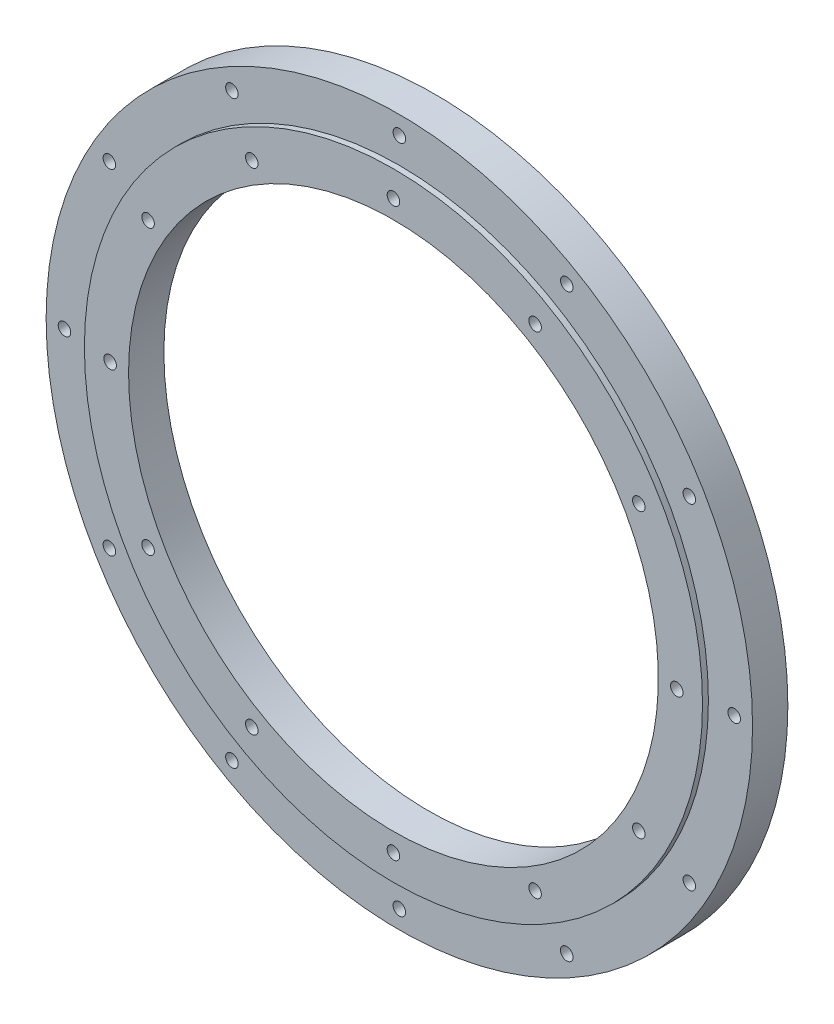
SolidWorks part; units mm, degrees
ref_plane "Front Plane" through (0, 0, 0) normal (0, 0, 1) x (1, 0, 0)
ref_plane "Top Plane" through (0, 0, 0) normal (0, 1, 0) x (1, 0, 0)
ref_plane "Right Plane" through (0, 0, 0) normal (1, 0, 0) x (0, 0, -1)
sketch "Sketch2" plane through (0, 0, 0) normal (0, 0, 1) x (1, 0, 0)
  circle A0 centre (0, 0) radius 76.2
  circle A1 centre (0, 0) radius 57.15
  circle A2 centre (0, 0) radius 66.675
  dimension "D1" = 114.3
  dimension "D2" = 133.35
  dimension "D3" = 152.4
extrude "Boss-Extrude1" add sketch "Sketch2" along normal blind 7.62 contours A0 A2 region at (-74.0447, 0, 0)
extrude "Boss-Extrude2" add sketch "Sketch2<3>" along normal blind 7.62 from offset 1.27 contours A2 A1 region at (-64.7891, 0, 0)
sketch "Sketch2<3>" plane through (0, 0, 0) normal (0, 0, 1) x (1, 0, 0) same geometry as "Sketch2"
hole_wizard "#6-32 Tapped Hole1" positions "3DSketch1" profile "Sketch3" tap size "#6-32" standard "ANSI Inch" end condition through all
sketch3d "3DSketch1"
  line L0 (0, 0, 8.89) -> (0, 0, 7.62) construction
  line L1 (0, 0, 8.89) -> (0, 0, 1.27) construction
  line L2 (0, 0, 8.89) -> (0, 66.675, 8.89) construction
  line L3 (0, 0, 8.89) -> (-33.3375, 57.7422, 8.89) construction
  line L4 (0, 0, 8.89) -> (-57.7422, 33.3375, 8.89) construction
  line L5 (0, 0, 8.89) -> (-66.675, 0, 8.89) construction
  line L6 (0, 0, 8.89) -> (-57.7422, -33.3375, 8.89) construction
  line L7 (0, 0, 8.89) -> (-33.3375, -57.7422, 8.89) construction
  line L8 (0, 0, 8.89) -> (0, -66.675, 8.89) construction
  line L9 (0, 0, 8.89) -> (33.3375, -57.7422, 8.89) construction
  line L10 (0, 0, 8.89) -> (57.7422, -33.3375, 8.89) construction
  line L11 (0, 0, 8.89) -> (66.675, 0, 8.89) construction
  line L12 (0, 0, 8.89) -> (57.7422, 33.3375, 8.89) construction
  line L13 (0, 0, 8.89) -> (33.3375, 57.7422, 8.89) construction
  circle A0 centre (0, 0, 8.89) radius 61.1251
  circle A1 centre (0, 0, 8.89) radius 66.675 construction
  point P0 (-30.5625, 52.9359, 8.89)
  point P2 (-52.9359, 30.5626, 8.89)
  point P4 (-61.1251, 0, 8.89)
  point P6 (-52.9359, -30.5625, 8.89)
  point P8 (-30.5626, -52.9359, 8.89)
  point P10 (0, -61.1251, 8.89)
  point P12 (30.5625, -52.9359, 8.89)
  point P14 (52.9359, -30.5626, 8.89)
  point P16 (61.1251, 0, 8.89)
  point P18 (52.9359, 30.5625, 8.89)
  point P20 (30.5626, 52.9359, 8.89)
  point P22 (0, 61.1251, 8.89)
  point P27 (0, 0, 70.0151)
  point P37 (0, 0, 75.565)
  dimension "D1" = 122.2502
  dimension "D2" = 30
  dimension "D3" = 30
  dimension "D4" = 30
  dimension "D5" = 30
  dimension "D6" = 30
  dimension "D7" = 30
  dimension "D8" = 30
  dimension "D9" = 30
  dimension "D10" = 30
  dimension "D11" = 30
  dimension "D12" = 30
  dimension "D13" = 30
sketch "Sketch3" plane through (-30.5625, 52.9359, 8.89) normal (1, 0, 0) x (0, -1, 0)
  line L0 (0, 0) -> (0, 8.89)
  line L1 (0, 8.89) -> (1.3525, 8.89)
  line L2 (1.3525, 8.89) -> (1.3525, 0)
  line L5 (1.3525, 0) -> (0, 0)
  line L11 (0, -6.35) -> (0, 107.95) construction
  dimension "Thru Tap Drill Dia." = 2.7051
  dimension "Thru Tap Drill Depth" = 8.89
cosmetic thread "Hole Thread1" parameters "D2"=3.5052
cosmetic thread "Hole Thread2" parameters "D2"=3.5052
cosmetic thread "Hole Thread3" parameters "D2"=3.5052
cosmetic thread "Hole Thread4" parameters "D2"=3.5052
cosmetic thread "Hole Thread5" parameters "D2"=3.5052
cosmetic thread "Hole Thread6" parameters "D2"=3.5052
cosmetic thread "Hole Thread7" parameters "D2"=3.5052
cosmetic thread "Hole Thread8" parameters "D2"=3.5052
cosmetic thread "Hole Thread9" parameters "D2"=3.5052
cosmetic thread "Hole Thread10" parameters "D2"=3.5052
cosmetic thread "Hole Thread11" parameters "D2"=3.5052
cosmetic thread "Hole Thread12" parameters "D2"=3.5052
hole_wizard "#6-32 Tapped Hole2" positions "3DSketch2" profile "Sketch4" tap size "#6-32" standard "ANSI Inch" end condition through all
sketch3d "3DSketch2"
  line L0 (0, 0, 7.62) -> (0, 0, 0) construction
  line L1 (0, 0, 8.89) -> (0, 0, 7.62) construction
  line L20 (0, 0, 7.62) -> (0, 76.2, 7.62) construction
  line L21 (0, 0, 7.62) -> (-38.1, 65.9911, 7.62) construction
  line L22 (0, 0, 7.62) -> (-65.9911, 38.1, 7.62) construction
  line L23 (0, 0, 7.62) -> (-76.2, 0, 7.62) construction
  line L24 (0, 0, 7.62) -> (-65.9911, -38.1, 7.62) construction
  line L25 (0, 0, 7.62) -> (-38.1, -65.9911, 7.62) construction
  line L26 (0, 0, 7.62) -> (0, -76.2, 7.62) construction
  line L27 (0, 0, 7.62) -> (38.1, -65.9911, 7.62) construction
  line L28 (0, 0, 7.62) -> (65.9911, -38.1, 7.62) construction
  line L29 (0, 0, 7.62) -> (76.2, 0, 7.62) construction
  line L30 (0, 0, 7.62) -> (65.9911, 38.1, 7.62) construction
  line L31 (0, 0, 7.62) -> (38.1, 65.9911, 7.62) construction
  circle A1 centre (0, 0, 7.62) radius 72.2376
  circle A3 centre (0, 0, 7.62) radius 76.2 construction
  point P0 (0, 72.2376, 7.62)
  point P2 (-36.1188, 62.5596, 7.62)
  point P4 (-62.5596, 36.1188, 7.62)
  point P6 (-72.2376, 0, 7.62)
  point P8 (-62.5596, -36.1188, 7.62)
  point P10 (-36.1188, -62.5596, 7.62)
  point P12 (0, -72.2376, 7.62)
  point P14 (36.1188, -62.5596, 7.62)
  point P16 (62.5596, -36.1188, 7.62)
  point P18 (72.2376, 0, 7.62)
  point P20 (62.5596, 36.1188, 7.62)
  point P22 (36.1188, 62.5596, 7.62)
  point P33 (0, 0, 79.8576)
  point P85 (0, 0, 83.82)
  dimension "D1" = 144.4752
  dimension "D2" = 30
  dimension "D3" = 30
  dimension "D4" = 30
  dimension "D5" = 30
  dimension "D6" = 30
  dimension "D7" = 30
  dimension "D8" = 30
  dimension "D9" = 30
  dimension "D10" = 30
  dimension "D11" = 30
  dimension "D12" = 30
  dimension "D13" = 30
sketch "Sketch4" plane through (0, 72.2376, 7.62) normal (1, 0, 0) x (0, -1, 0)
  line L0 (0, 0) -> (0, 7.62)
  line L1 (0, 7.62) -> (1.3525, 7.62)
  line L2 (1.3525, 7.62) -> (1.3525, 0)
  line L5 (1.3525, 0) -> (0, 0)
  line L11 (0, -6.35) -> (0, 107.95) construction
  dimension "Thru Tap Drill Dia." = 2.7051
  dimension "Thru Tap Drill Depth" = 7.62
cosmetic thread "Hole Thread13" parameters "D2"=3.5052
cosmetic thread "Hole Thread14" parameters "D2"=3.5052
cosmetic thread "Hole Thread15" parameters "D2"=3.5052
cosmetic thread "Hole Thread16" parameters "D2"=3.5052
cosmetic thread "Hole Thread17" parameters "D2"=3.5052
cosmetic thread "Hole Thread18" parameters "D2"=3.5052
cosmetic thread "Hole Thread19" parameters "D2"=3.5052
cosmetic thread "Hole Thread20" parameters "D2"=3.5052
cosmetic thread "Hole Thread21" parameters "D2"=3.5052
cosmetic thread "Hole Thread22" parameters "D2"=3.5052
cosmetic thread "Hole Thread23" parameters "D2"=3.5052
cosmetic thread "Hole Thread24" parameters "D2"=3.5052
